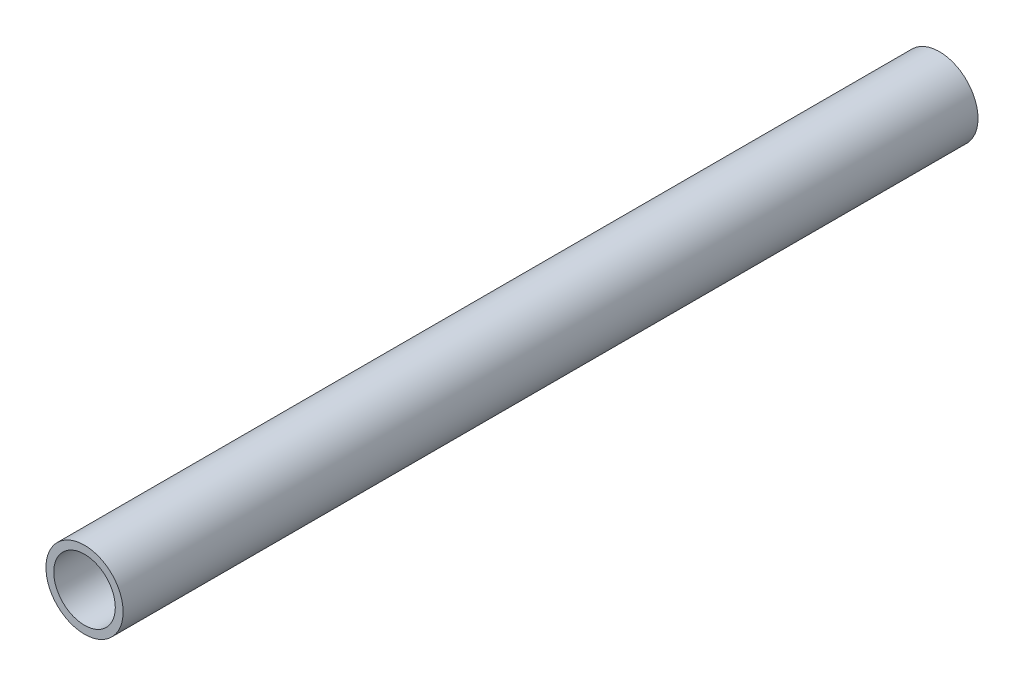
SolidWorks part; units mm, degrees
ref_plane "Front" through (0, 0, 0) normal (0, 0, 1) x (1, 0, 0)
ref_plane "Top" through (0, 0, 0) normal (0, 1, 0) x (1, 0, 0)
ref_plane "Right" through (0, 0, 0) normal (1, 0, 0) x (0, 0, -1)
sketch "Sketch1" plane through (0, 0, 0) normal (0, 0, 1) x (1, 0, 0)
  circle A0 centre (0, 0) radius 16.7005
  circle A1 centre (0, 0) radius 13.3223
  dimension "D1" = 33.401
  dimension "D2" = 26.6446
extrude "Boss-Extrude1" add sketch "Sketch1" along normal mid plane 370
